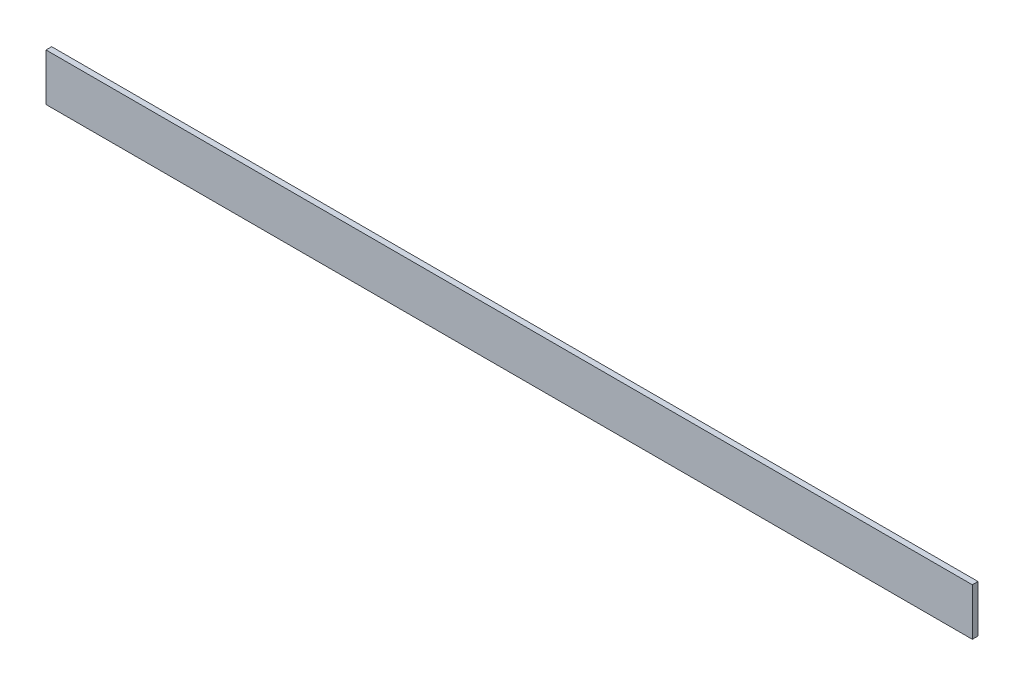
SolidWorks part; units mm, degrees
ref_plane "Спереди" through (0, 0, 0) normal (0, 0, 1) x (1, 0, 0)
ref_plane "Сверху" through (0, 0, 0) normal (0, 1, 0) x (1, 0, 0)
ref_plane "Справа" through (0, 0, 0) normal (1, 0, 0) x (0, 0, -1)
sketch "Эскиз1" plane through (0, 0, 0) normal (1, 0, 0) x (0, 0, -1)
  line L0 (0, 0) -> (25, 0)
  line L1 (0, 0) -> (0, 25)
extrude "Вытянуть-Тонкостенный1" add sketch "Эскиз1" along normal blind 490 thin thin type one direction wall 3
sketch "Эскиз2" plane through (0, 0, 0) normal (0, -1, 0) x (1, 0, 0)
  line L0 (245, 11.0201) -> (245, -25) construction
  line L1 (0, -25) -> (22, -25)
  line L2 (0, -25) -> (0, -3)
  line L3 (0, -3) -> (22, -3)
  line L4 (22, -25) -> (22, -3)
  line L5 (490, -25) -> (0, -25) construction
  line L6 (468, -25) -> (468, -3)
  line L7 (490, -3) -> (468, -3)
  line L8 (490, -25) -> (490, -3)
  line L9 (490, -25) -> (468, -25)
extrude "Вырез-Вытянуть1" cut sketch "Эскиз2" against normal through all
